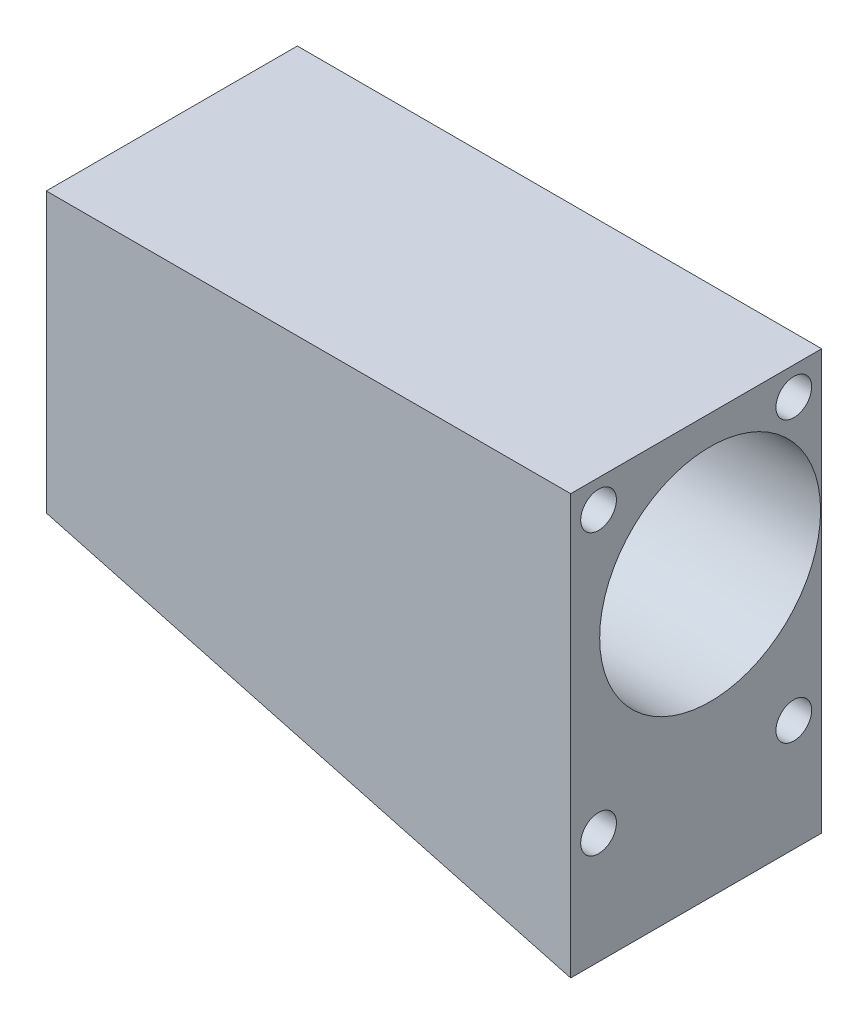
SolidWorks part; units mm, degrees
ref_plane "Front Plane" through (0, 0, 0) normal (0, 0, 1) x (1, 0, 0)
ref_plane "Top Plane" through (0, 0, 0) normal (0, 1, 0) x (1, 0, 0)
ref_plane "Right Plane" through (0, 0, 0) normal (1, 0, 0) x (0, 0, -1)
sketch "Sketch1" plane through (0, 0, 0) normal (0, 0, 1) x (1, 0, 0)
  line L1 (0, 0) -> (57.15, 0)
  line L2 (0, 0) -> (0, 31.75)
  line L3 (0, 31.75) -> (57.15, 31.75)
  line L4 (57.15, 0) -> (57.15, 31.75)
  dimension "D1" = 31.75
  dimension "D2" = 57.15
extrude "Boss-Extrude1" add sketch "Sketch1" against normal blind 28.575
sketch "Sketch2" plane through (0, 0, 0) normal (-1, 0, 0) x (0, 0, 1)
  line L2 (-28.575, 31.75) -> (-28.575, 0) construction
  circle A0 centre (-15.875, 15.875) radius 12.573
  point P6 (-28.575, 15.875)
  dimension "D1" = 12.7
  dimension "D2" = 25.146
extrude "Cut-Extrude1" cut sketch "Sketch2" against normal through all
sketch "Sketch3" plane through (0, 31.75, 0) normal (0, 1, 0) x (1, 0, 0)
  line L1 (0, 28.575) -> (-2.54, 28.575)
  line L2 (0, 28.575) -> (0, 0)
  line L3 (0, 0) -> (-2.54, 0)
  line L4 (-2.54, 28.575) -> (-2.54, 0)
  dimension "D1" = 2.54
  dimension "D2" = 28.575
extrude "Boss-Extrude2" add sketch "Sketch3" against normal blind 31.75
sketch "Sketch4" plane through (-2.54, 0, 0) normal (-1, 0, 0) x (0, 0, 1)
  line L0 (-28.575, 0) -> (-28.575, 31.75) construction
  circle A0 centre (-15.875, 15.875) radius 9.525
  point P5 (-28.575, 15.875)
  dimension "D1" = 19.05
  dimension "D2" = 12.7
extrude "Cut-Extrude2" cut sketch "Sketch4" against normal up to surface (2.54 mm away) up to face at (0, 15.875, -28.448)
sketch "Sketch5" plane through (0, 0, 0) normal (0, 0, 1) x (1, 0, 0)
  line L0 (-2.54, 0) -> (57.15, 0)
  line L1 (57.15, 0) -> (57.15, -15.9939)
  line L2 (57.15, -15.9939) -> (-2.54, 0)
  dimension "D1" = 15
extrude "Boss-Extrude3" add sketch "Sketch5" against normal blind 28.575
sketch "Sketch6" plane through (57.15, 0, 0) normal (1, 0, 0) x (0, 0, -1)
  line L0 (0, -15.9939) -> (0, 31.75) construction
  line L1 (28.575, 31.75) -> (0, 31.75) construction
  line L2 (28.575, -15.9939) -> (28.575, 31.75) construction
  line L3 (28.575, -15.9939) -> (0, -15.9939) construction
  circle A0 centre (3.175, 28.575) radius 2.032
  circle A1 centre (25.4, 28.575) radius 2.032
  circle A2 centre (25.4, -3.2939) radius 2.032
  circle A3 centre (3.175, -3.2939) radius 2.032
  dimension "D1" = 4.064
  dimension "D2" = 3.175
  dimension "D3" = 3.175
  dimension "D4" = 3.175
  dimension "D5" = 12.7
extrude "Cut-Extrude3" cut sketch "Sketch6" against normal blind 12.7
